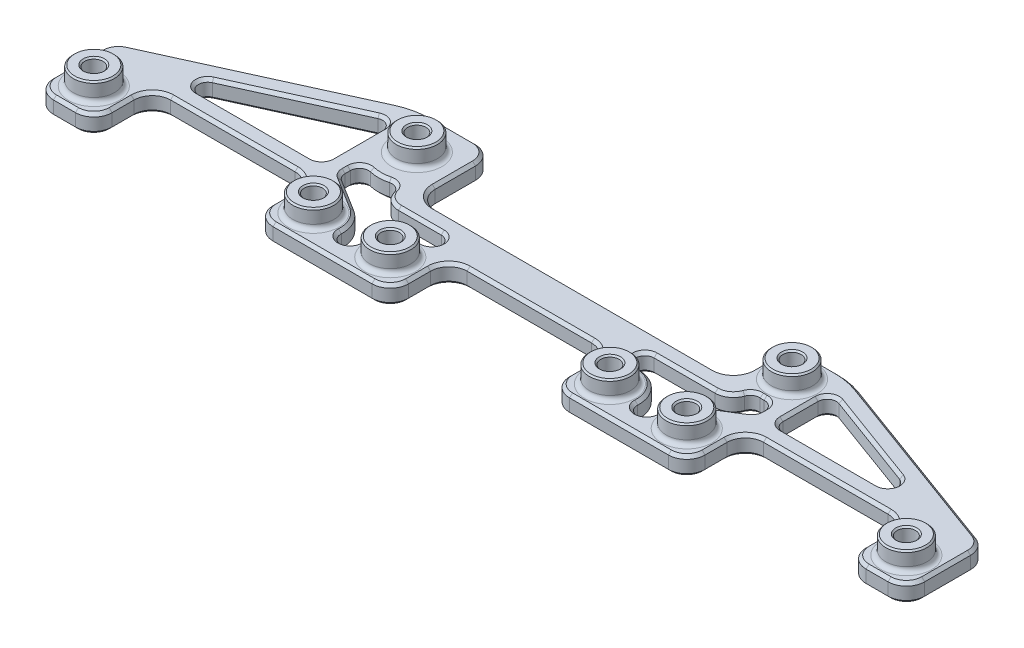
SolidWorks part; units mm, degrees
ref_plane "Front" through (0, 0, 0) normal (0, 0, 1) x (1, 0, 0)
ref_plane "Top" through (0, 0, 0) normal (0, 1, 0) x (1, 0, 0)
ref_plane "Right" through (0, 0, 0) normal (1, 0, 0) x (0, 0, -1)
sketch "Sketch2" plane through (0, 0, 0) normal (0, 1, 0) x (1, 0, 0)
  line L0 (-25.8699, 13.3477) -> (-25.8699, 8.7313) construction
  line L5 (-33.6614, 16.5227) -> (-29.0449, 16.5227) construction
  line L8 (52.7861, 4.9827) -> (53.8806, 7.9631) construction
  line L9 (-38.4239, 3.175) -> (38.4238, 3.175) construction
  line L12 (-68.58, -13.335) -> (-69.215, -13.335) construction
  line L13 (-65.405, -9.525) -> (-65.405, -10.16) construction
  line L14 (-27.305, -10.16) -> (-24.13, -10.16) construction
  line L15 (-28.0988, -3.175) -> (-74.7712, -3.175) construction
  line L20 (-37.465, -10.16) -> (-37.465, -9.525) construction
  line L21 (-13.97, -9.525) -> (-13.97, -10.16) construction
  line L22 (13.97, -10.16) -> (13.97, -9.525) construction
  line L23 (37.465, -9.525) -> (37.465, -10.16) construction
  line L28 (37.6301, 13.3477) -> (32.2199, 13.3477) construction
  line L29 (65.405, -10.16) -> (65.405, -9.525) construction
  line L32 (29.0449, 8.7313) -> (29.0449, 10.1727) construction
  line L33 (-37.465, -13.335) -> (-27.305, -13.335) construction
  line L36 (-75.565, 0) -> (75.565, 0) construction
  line L37 (-75.565, -13.335) -> (-65.405, -13.335) construction
  line L38 (-75.565, -13.335) -> (-75.565, -3.175) construction
  line L39 (-75.565, -3.175) -> (-65.405, -3.175) construction
  line L40 (-65.405, -13.335) -> (-65.405, -3.175) construction
  line L41 (-75.565, -13.335) -> (-65.405, -3.175) construction
  line L42 (-37.465, -13.335) -> (-37.465, -3.175) construction
  line L43 (-75.565, -3.175) -> (-65.405, -13.335) construction
  line L44 (-39.2176, 3.175) -> (-25.8699, 3.175) construction
  line L45 (-39.2176, 3.175) -> (-39.2176, 16.5227) construction
  line L46 (-39.2176, 16.5227) -> (-25.8699, 16.5227) construction
  line L47 (-25.8699, 3.175) -> (-25.8699, 16.5227) construction
  line L64 (-25.8699, 16.5227) -> (-39.2176, 16.5227)
  line L67 (-39.2176, 3.175) -> (-25.8699, 16.5227) construction
  line L69 (-75.565, -13.335) -> (-65.405, -13.335)
  line L70 (-65.405, -13.335) -> (-65.405, -3.175)
  line L71 (-65.405, -3.175) -> (-37.465, -3.175)
  line L72 (-37.465, -3.175) -> (-37.465, -13.335)
  line L73 (-37.465, -13.335) -> (-13.97, -13.335)
  line L74 (-13.97, -13.335) -> (-13.97, -3.175)
  line L75 (-13.97, -3.175) -> (13.97, -3.175)
  line L76 (13.97, -3.175) -> (13.97, -13.335)
  line L77 (13.97, -13.335) -> (37.465, -13.335)
  line L78 (37.465, -13.335) -> (37.465, -3.175)
  line L79 (37.465, -3.175) -> (65.405, -3.175)
  line L80 (65.405, -3.175) -> (65.405, -13.335)
  line L81 (65.405, -13.335) -> (75.565, -13.335)
  line L85 (39.2176, 13.3477) -> (29.0449, 13.3477)
  line L86 (-25.8699, 16.5227) -> (-25.8699, 3.175)
  line L87 (-25.8699, 3.175) -> (29.0449, 3.175)
  line L88 (29.0449, 3.175) -> (29.0449, 13.3477)
  line L89 (-39.2176, 16.5227) -> (-25.8699, 3.175) construction
  line L90 (-75.565, 0) -> (75.565, 0) construction
  line L91 (-39.2176, 16.5227) -> (-75.565, 0)
  line L92 (-75.565, 0) -> (-75.565, -13.335)
  line L93 (-39.2176, 13.0351) -> (-39.2176, 0)
  line L94 (-24.13, -3.175) -> (-13.97, -3.175) construction
  line L95 (-39.2176, 0) -> (-67.8927, 0)
  line L96 (-67.8927, 0) -> (-39.2176, 13.0351)
  line L97 (-53.5552, 6.5175) -> (-54.8691, 9.4079) construction
  line L98 (39.2176, 13.3477) -> (75.565, 0)
  line L99 (65.405, -13.335) -> (75.565, -13.335) construction
  line L100 (65.405, -13.335) -> (65.405, -3.175) construction
  line L101 (65.405, -3.175) -> (75.565, -3.175) construction
  line L102 (75.565, -13.335) -> (75.565, -3.175) construction
  line L103 (65.405, -13.335) -> (75.565, -3.175) construction
  line L104 (65.405, -3.175) -> (75.565, -13.335) construction
  line L105 (29.0449, 3.175) -> (39.2176, 3.175) construction
  line L106 (29.0449, 3.175) -> (29.0449, 13.3477) construction
  line L107 (29.0449, 13.3477) -> (39.2176, 13.3477) construction
  line L108 (39.2176, 3.175) -> (39.2176, 13.3477) construction
  line L109 (29.0449, 3.175) -> (39.2176, 13.3477) construction
  line L110 (29.0449, 13.3477) -> (39.2176, 3.175) construction
  line L111 (75.565, 0) -> (75.565, -13.335)
  line L112 (39.2176, 9.9654) -> (39.2176, 0)
  line L113 (-24.13, -3.175) -> (-24.13, -13.335) construction
  line L114 (39.2176, 0) -> (66.3546, 0)
  line L115 (66.3546, 0) -> (39.2176, 9.9654)
  line L116 (-37.465, -3.175) -> (-27.305, -3.175) construction
  line L117 (-27.305, -13.335) -> (-27.305, -3.175) construction
  line L118 (-24.13, -13.335) -> (-13.97, -13.335) construction
  line L119 (-13.97, -3.175) -> (-13.97, -13.335) construction
  line L120 (-25.7175, -10.16) -> (-25.7175, -13.335) construction
  line L125 (-36.0426, 0) -> (-36.0426, 4.1657) construction
  line L126 (-36.0426, 2.0828) -> (-39.2176, 2.0828) construction
  line L127 (-27.305, -10.16) -> (-27.6757, -10.16) construction
  line L128 (-24.13, -10.16) -> (-23.7593, -10.16) construction
  line L129 (23.7593, -10.16) -> (27.6757, -10.16) construction
  line L130 (25.7175, -10.16) -> (25.7175, -13.335) construction
  line L131 (23.7593, -10.16) -> (27.6757, -10.16)
  line L132 (36.0426, 3.175) -> (36.0426, 0) construction
  line L133 (-25.8699, 3.175) -> (-25.8699, -10.16) construction
  line L134 (36.0426, 1.5875) -> (39.2176, 1.5875) construction
  line L135 (36.0426, 3.5478) -> (36.0426, 0)
  line L136 (36.0426, 0) -> (29.7032, -3.9406)
  line L137 (29.0449, 0) -> (13.97, 0)
  line L138 (-67.8927, 0) -> (-75.565, -3.4876) construction
  line L139 (-72.39, -3.175) -> (-72.39, -3.5457) construction
  line L144 (-36.0426, 4.1657) -> (-36.0426, 0)
  line L147 (-27.6757, -10.16) -> (-23.7593, -10.16)
  line L148 (-29.7032, -3.9406) -> (-36.0426, 0)
  line L149 (-13.97, 0) -> (-25.8699, 0)
  line L151 (-72.39, -3.3604) -> (-75.565, -3.3604) construction
  line L152 (-72.39, -3.175) -> (-72.39, 1.4433) construction
  circle A0 centre (-32.5438, 9.8489) radius 6.6738 construction
  circle A1 centre (-32.385, -8.255) radius 5.08 construction
  circle A2 centre (-19.05, -8.255) radius 5.08 construction
  arc A4 (-27.6757, -10.16) -> (-29.7032, -3.9406) centre (-32.385, -8.255) ccw
  circle A6 centre (-25.8699, 3.175) radius 3.175 construction
  arc A8 (-36.0426, 4.1657) -> (-28.84, 4.297) centre (-32.5438, 9.8489) ccw
  arc A9 (-28.84, 4.297) -> (-25.8699, 0) centre (-25.8699, 3.175) ccw
  circle A10 centre (-13.97, -3.175) radius 3.175 construction
  arc A11 (-13.97, 0) -> (-17.1222, -3.555) centre (-13.97, -3.175) ccw
  arc A12 (-23.7593, -10.16) -> (-17.1222, -3.555) centre (-19.05, -8.255) cw
  circle A13 centre (34.1312, 8.2614) radius 5.0863 construction
  circle A14 centre (19.05, -8.255) radius 5.08 construction
  circle A15 centre (32.385, -8.255) radius 5.08 construction
  circle A16 centre (13.97, -3.175) radius 3.175 construction
  circle A17 centre (29.0449, 3.175) radius 3.175 construction
  arc A18 (27.6757, -10.16) -> (29.7032, -3.9406) centre (32.385, -8.255) cw
  arc A19 (36.0426, 3.5478) -> (32.1968, 3.5572) centre (34.1312, 8.2614) cw
  arc A20 (32.1968, 3.5572) -> (29.0449, 0) centre (29.0449, 3.175) cw
  arc A21 (13.97, 0) -> (17.1222, -3.555) centre (13.97, -3.175) cw
  arc A22 (17.1222, -3.555) -> (23.7593, -10.16) centre (19.05, -8.255) cw
  circle A23 centre (-70.485, -8.255) radius 5.08 construction
  circle A24 centre (-67.8927, 0) radius 3.175 construction
  circle A25 centre (-65.405, -3.175) radius 3.175 construction
  circle A26 centre (-75.565, 0) radius 3.175 construction
  point P4 (-32.5438, 9.8489)
  point P18 (70.485, -8.255)
  point P20 (34.1312, 8.2614)
  point P78 (-70.485, -8.255)
  point P91 (-32.385, -3.175)
  dimension "D2" = 6.35
  dimension "D1" = 3.175
extrude "Boss-Extrude2" add sketch "Sketch2" along normal blind 3.175
sketch "Sketch4" plane through (0, 3.175, 0) normal (0, 1, 0) x (1, 0, 0)
  line L0 (-75.565, -13.335) -> (-65.405, -13.335) construction
  line L1 (-75.565, 0) -> (-75.565, -13.335) construction
  line L2 (-65.405, -13.335) -> (-65.405, -3.175) construction
  line L3 (65.405, -3.175) -> (65.405, -13.335) construction
  line L4 (65.405, -13.335) -> (75.565, -13.335) construction
  line L5 (75.565, -13.335) -> (75.565, 0) construction
  circle A0 centre (-70.485, -8.255) radius 5.08 construction
  circle A1 centre (-32.385, -8.255) radius 3.5719
  arc A2 (-27.6757, -10.16) -> (-29.7032, -3.9406) centre (-32.385, -8.255) ccw construction
  circle A3 centre (-19.05, -8.255) radius 3.5719
  arc A4 (-17.1222, -3.555) -> (-23.7593, -10.16) centre (-19.05, -8.255) ccw construction
  circle A5 centre (19.05, -8.255) radius 3.5719
  arc A6 (23.7593, -10.16) -> (17.1222, -3.555) centre (19.05, -8.255) ccw construction
  circle A7 centre (70.485, -8.255) radius 5.08 construction
  circle A8 centre (70.485, -8.255) radius 3.5719
  circle A9 centre (-70.485, -8.255) radius 3.5719
  circle A10 centre (32.385, -8.255) radius 3.5719
  arc A11 (29.7032, -3.9406) -> (27.6757, -10.16) centre (32.385, -8.255) ccw construction
  circle A12 centre (-32.5438, 9.8489) radius 3.5719
  arc A13 (-36.0426, 4.1657) -> (-28.84, 4.297) centre (-32.5438, 9.8489) ccw construction
  circle A14 centre (34.1312, 8.2614) radius 3.5719
  arc A15 (32.1968, 3.5572) -> (36.0426, 3.5478) centre (34.1312, 8.2614) ccw construction
  dimension "D1" = 7.1437
extrude "Boss-Extrude3" add sketch "Sketch4" along normal blind 3.175
sketch "Sketch3" plane through (0, 0, 0) normal (0, 1, 0) x (1, 0, 0)
  circle A0 centre (-70.485, -8.255) radius 1.5875 construction
  circle A1 centre (-70.485, -8.255) radius 1.5875
  circle A2 centre (-32.5438, 9.8489) radius 1.5875 construction
  circle A3 centre (34.1312, 8.2614) radius 1.5875 construction
  circle A4 centre (70.485, -8.255) radius 1.5875 construction
  circle A5 centre (32.385, -8.255) radius 1.5875 construction
  circle A6 centre (19.05, -8.255) radius 1.5875 construction
  circle A7 centre (-19.05, -8.255) radius 1.5875 construction
  circle A8 centre (-32.385, -8.255) radius 1.5875 construction
  circle A9 centre (-32.5438, 9.8489) radius 1.5875
  circle A10 centre (34.1312, 8.2614) radius 1.5875
  circle A11 centre (70.485, -8.255) radius 1.5875
  circle A12 centre (32.385, -8.255) radius 1.5875
  circle A13 centre (19.05, -8.255) radius 1.5875
  circle A14 centre (-19.05, -8.255) radius 1.5875
  circle A15 centre (-32.385, -8.255) radius 1.5875
extrude "Cut-Extrude1" cut sketch "Sketch3" along normal up to next
fillet "Fillet3" radius 12.7 2 edges at (-39.2176, 1.5875, -16.5227) (39.2176, 1.5875, -13.3477)
fillet "Fillet1" radius 3.175 20 edges at (-75.565, 1.5875, 13.335) (-75.565, 1.5875, 0) (-25.8699, 1.5875, -16.5227) (-25.8699, 1.5875, -3.175) (29.0449, 1.5875, -3.175) (29.0449, 1.5875, -13.3477) (75.565, 1.5875, 0) (75.565, 1.5875, 13.335) (65.405, 1.5875, 13.335) (65.405, 1.5875, 3.175) (37.465, 1.5875, 3.175) (37.465, 1.5875, 13.335) (13.97, 1.5875, 13.335) (13.97, 1.5875, 3.175) (-13.97, 1.5875, 3.175) (-13.97, 1.5875, 13.335) (-37.465, 1.5875, 13.335) (-37.465, 1.5875, 3.175) (-65.405, 1.5875, 3.175) (-65.405, 1.5875, 13.335)
fillet "Fillet2" radius 1.5875 20 edges at (39.2176, 1.5875, 0) (66.3546, 1.5875, 0) (39.2176, 1.5875, -9.9654) (-67.8927, 1.5875, 0) (-39.2176, 1.5875, 0) (-39.2176, 1.5875, -13.0351) (-27.6757, 1.5875, 10.16) (-36.0426, 1.5875, 0) (-28.84, 1.5875, -4.297) (-36.0426, 1.5875, -4.1657) (-23.7593, 1.5875, 10.16) (-17.1222, 1.5875, 3.555) (-13.97, 1.5875, 0) (23.7593, 1.5875, 10.16) (27.6757, 1.5875, 10.16) (36.0426, 1.5875, 0) (36.0426, 1.5875, -3.5478) (13.97, 1.5875, 0) (17.1222, 1.5875, 3.555) (32.1968, 1.5875, -3.5572)
fillet "Fillet5" radius 0.7937 8 edges at (70.485, 3.175, 4.6831) (19.05, 3.175, 4.6831) (-19.05, 3.175, 4.6831) (-32.385, 3.175, 4.6831) (-70.485, 3.175, 4.6831) (32.385, 3.175, 4.6831) (34.1312, 3.175, -11.8332) (-32.5438, 3.175, -13.4207)
chamfer "Chamfer1" distance 0.508 angle 45 176 edges at (30.8854, 0, -0.5879) (32.6817, 0, -2.9462) (34.0307, 0, -3.176) (35.5501, 0, -2.7448) (36.0426, 0, -1.2389) (35.8427, 0, -0.1111) (32.4982, 0, 2.2032) (27.8873, 0, 5.8934) (26.874, 0, 9.668) (25.7175, 0, 10.16) (24.561, 0, 9.668) (22.5703, 0, 4.5925) (17.6061, 0, 2.9454) (16.9664, 0, 2.1251) (17.1639, 0, 0.671) (23.7525, 0, 0) (-29.6621, 0, -3.2381) (-27.7795, 0, -0.6385) (-22.165, 0, 0) (-17.1639, 0, 0.671) (-16.9664, 0, 2.1251) (-17.6061, 0, 2.9454) (-22.5703, 0, 4.5925) (-24.561, 0, 9.668) (-25.7175, 0, 10.16) (-26.874, 0, 9.668) (-27.8873, 0, 5.8934) (-32.4982, 0, 2.2032) (-35.8427, 0, -0.1111) (-36.0426, 0, -1.347) (-35.4392, 0, -3.0573) (-32.4664, 0, -3.1754) (39.8964, 0, -8.993) (49.663, 0, -6.1296) (58.9894, 0, -1.3096) (49.1157, 0, 0) (39.6826, 0, -0.465) (39.2176, 0, -4.6394) (-62.1158, 0, -1.2514) (-51.3417, 0, -7.5237) (-39.9457, 0, -11.9043) (-39.2176, 0, -6.0785) (-39.6826, 0, -0.465) (-50.6847, 0, 0) (-66.3349, 0, 12.4051) (-65.405, 0, 8.255) (-64.4751, 0, 4.1049) (-51.435, 0, 3.175) (-38.3949, 0, 4.1049) (-37.465, 0, 8.255) (-36.5351, 0, 12.4051) (-25.7175, 0, 13.335) (-14.8999, 0, 12.4051) (-13.97, 0, 8.255) (-13.0401, 0, 4.1049) (0, 0, 3.175) (13.0401, 0, 4.1049) (13.97, 0, 8.255) (14.8999, 0, 12.4051) (25.7175, 0, 13.335) (36.5351, 0, 12.4051) (37.465, 0, 8.255) (38.3949, 0, 4.1049) (51.435, 0, 3.175) (64.4751, 0, 4.1049) (65.405, 0, 8.255) (66.3349, 0, 12.4051) (70.485, 0, 13.335) (74.6351, 0, 12.4051) (75.565, 0, 6.1882) (74.9934, 0, 0.399) (57.4109, 0, -6.6666) (39.1827, 0, -13.1516) (34.5897, 0, -13.3477) (29.9748, 0, -12.4178) (29.0449, 0, -8.2614) (28.115, 0, -4.1049) (1.5875, 0, -3.175) (-24.94, 0, -4.1049) (-25.8699, 0, -9.8489) (-26.7998, 0, -15.5928) (-32.7557, 0, -16.5227) (-39.1552, 0, -16.2348) (-57.713, 0, -8.1151) (-75.0595, 0, 0.3255) (-75.565, 0, 6.1022) (-74.6351, 0, 12.4051) (-70.485, 0, 13.335) (24.561, 3.175, 9.668) (25.7175, 3.175, 10.16) (26.874, 3.175, 9.668) (27.8873, 3.175, 5.8934) (32.4982, 3.175, 2.2032) (35.8427, 3.175, -0.1111) (36.0426, 3.175, -1.2389) (35.5501, 3.175, -2.7448) (34.0307, 3.175, -3.176) (32.6817, 3.175, -2.9462) (30.8854, 3.175, -0.5879) (23.7525, 3.175, 0) (17.1639, 3.175, 0.671) (16.9664, 3.175, 2.1251) (17.6061, 3.175, 2.9454) (22.5703, 3.175, 4.5925) (39.8964, 3.175, -8.993) (39.2176, 3.175, -4.6394) (39.6826, 3.175, -0.465) (49.1157, 3.175, 0) (58.9894, 3.175, -1.3096) (49.663, 3.175, -6.1296) (-75.0595, 3.175, 0.3255) (-57.713, 3.175, -8.1151) (-39.1552, 3.175, -16.2348) (-32.7557, 3.175, -16.5227) (-26.7998, 3.175, -15.5928) (-25.8699, 3.175, -9.8489) (-24.94, 3.175, -4.1049) (1.5875, 3.175, -3.175) (28.115, 3.175, -4.1049) (29.0449, 3.175, -8.2614) (29.9748, 3.175, -12.4178) (34.5897, 3.175, -13.3477) (39.1827, 3.175, -13.1516) (57.4109, 3.175, -6.6666) (74.9934, 3.175, 0.399) (75.565, 3.175, 6.1882) (74.6351, 3.175, 12.4051) (70.485, 3.175, 13.335) (66.3349, 3.175, 12.4051) (65.405, 3.175, 8.255) (64.4751, 3.175, 4.1049) (51.435, 3.175, 3.175) (38.3949, 3.175, 4.1049) (37.465, 3.175, 8.255) (36.5351, 3.175, 12.4051) (25.7175, 3.175, 13.335) (14.8999, 3.175, 12.4051) (13.97, 3.175, 8.255) (13.0401, 3.175, 4.1049) (0, 3.175, 3.175) (-13.0401, 3.175, 4.1049) (-13.97, 3.175, 8.255) (-14.8999, 3.175, 12.4051) (-25.7175, 3.175, 13.335) (-36.5351, 3.175, 12.4051) (-37.465, 3.175, 8.255) (-38.3949, 3.175, 4.1049) (-51.435, 3.175, 3.175) (-64.4751, 3.175, 4.1049) (-66.3349, 3.175, 12.4051) (-74.6351, 3.175, 12.4051) (-62.1158, 3.175, -1.2514) (-50.6847, 3.175, 0) (-39.6826, 3.175, -0.465) (-39.2176, 3.175, -6.0785) (-39.9457, 3.175, -11.9043) (-51.3417, 3.175, -7.5237) (-27.8873, 3.175, 5.8934) (-26.874, 3.175, 9.668) (-25.7175, 3.175, 10.16) (-24.561, 3.175, 9.668) (-22.5703, 3.175, 4.5925) (-17.6061, 3.175, 2.9454) (-16.9664, 3.175, 2.1251) (-17.1639, 3.175, 0.671) (-22.165, 3.175, 0) (-27.7795, 3.175, -0.6385) (-29.6621, 3.175, -3.2381) (-32.4664, 3.175, -3.1754) (-35.4392, 3.175, -3.0573) (-36.0426, 3.175, -1.347) (-35.8427, 3.175, -0.1111) (-32.4982, 3.175, 2.2032) (-65.405, 3.175, 8.255) (-70.485, 3.175, 13.335) (-75.565, 3.175, 6.1022)
chamfer "Chamfer2" distance 0.254 angle 45 24 edges at (70.485, 0, 9.8425) (70.485, 6.35, 9.8425) (32.385, 0, 9.8425) (32.385, 6.35, 9.8425) (19.05, 0, 9.8425) (19.05, 6.35, 9.8425) (34.1312, 0, -6.6739) (-19.05, 0, 9.8425) (-19.05, 6.35, 9.8425) (-32.5438, 0, -8.2614) (-32.385, 0, 9.8425) (-32.385, 6.35, 9.8425) (-70.485, 0, 9.8425) (-70.485, 6.35, 9.8425) (70.485, 6.35, 11.8269) (32.385, 6.35, 11.8269) (19.05, 6.35, 11.8269) (-19.05, 6.35, 11.8269) (-32.385, 6.35, 11.8269) (-70.485, 6.35, 11.8269) (34.1312, 6.35, -6.6739) (-32.5438, 6.35, -8.2614) (34.1312, 6.35, -4.6895) (-32.5438, 6.35, -6.277)
